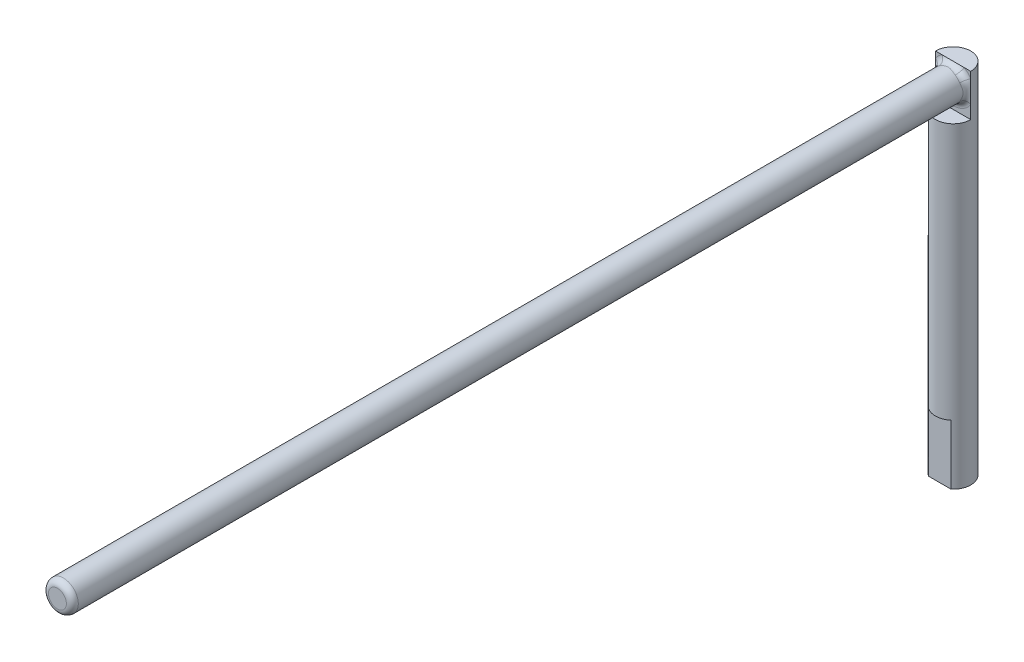
SolidWorks part; units mm, degrees
ref_plane "Front Plane" through (0, 0, 0) normal (0, 0, 1) x (1, 0, 0)
ref_plane "Top Plane" through (0, 0, 0) normal (0, 1, 0) x (1, 0, 0)
ref_plane "Right Plane" through (0, 0, 0) normal (1, 0, 0) x (0, 0, -1)
sketch "Sketch1" plane through (0, 0, 0) normal (0, 1, 0) x (1, 0, 0)
  circle A0 centre (0, 0) radius 2.95
  dimension "D1" = 5.9
extrude "Boss-Extrude1" add sketch "Sketch1" along normal blind 60
sketch "Sketch2" plane through (0, 0, 0) normal (0, -1, 0) x (1, 0, 0)
  line L1 (-3.4357, 5.4336) -> (3.2005, 5.4336)
  line L2 (-3.4357, 5.4336) -> (-3.4357, 2.2544)
  line L3 (-3.4357, 2.2544) -> (3.2005, 2.2544)
  line L4 (3.2005, 5.4336) -> (3.2005, 2.2544)
extrude "Cut-Extrude1" cut sketch "Sketch2" against normal blind 10
sketch "Sketch5" plane through (0, 60, 0) normal (0, 1, 0) x (1, 0, 0)
  line L1 (-3.994, 0) -> (4.0632, 0)
  line L2 (-3.994, 0) -> (-3.994, -3.7617)
  line L3 (-3.994, -3.7617) -> (4.0632, -3.7617)
  line L4 (4.0632, 0) -> (4.0632, -3.7617)
extrude "Cut-Extrude2" cut sketch "Sketch5" against normal blind 7
sketch "Sketch6" plane through (0, 0, 0) normal (0, 0, 1) x (1, 0, 0)
  circle A0 centre (0, 57.05) radius 2.5
  dimension "D3" = 5
extrude "Boss-Extrude2" add sketch "Sketch6" along normal blind 150
fillet "Fillet1" radius 1 2 edges at (-2.5, 57.05, 0) (2.5, 57.05, 150)
